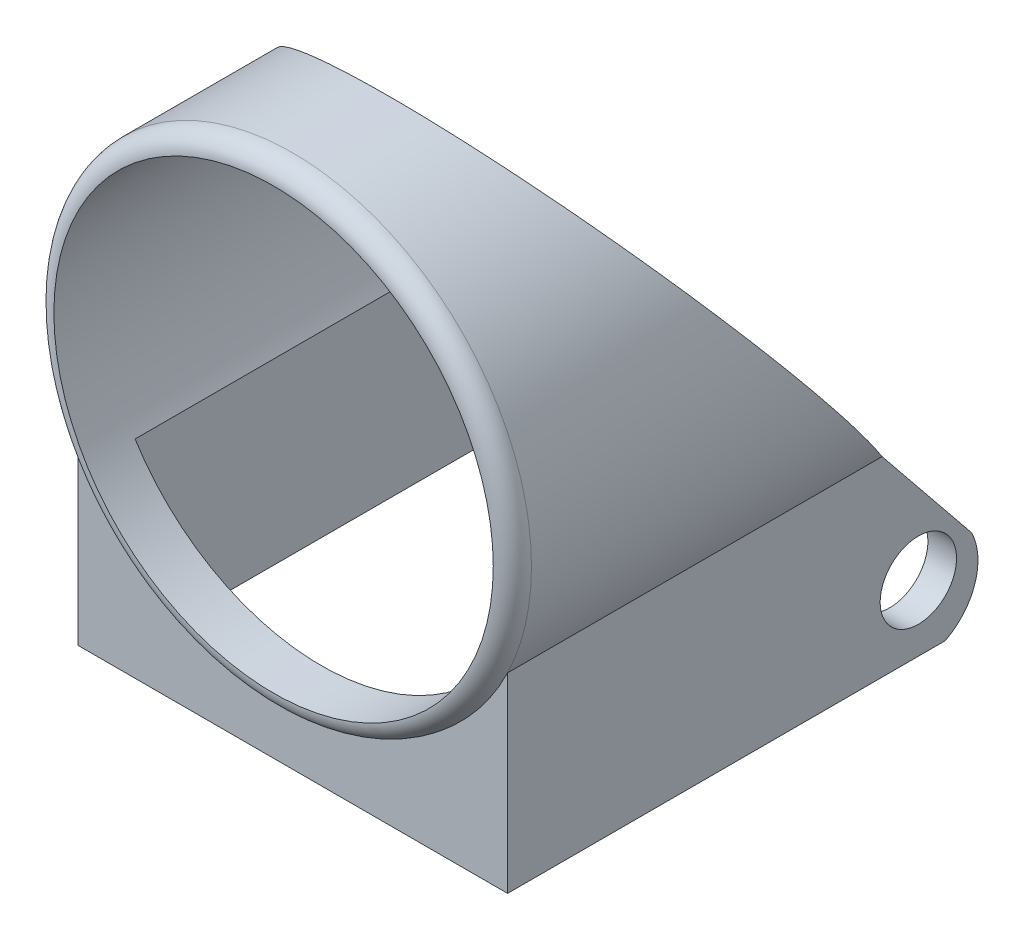
SolidWorks part; units mm, degrees
ref_plane "前视基准面" through (0, 0, 0) normal (0, 0, 1) x (1, 0, 0)
ref_plane "上视基准面" through (0, 0, 0) normal (0, 1, 0) x (1, 0, 0)
ref_plane "右视基准面" through (0, 0, 0) normal (1, 0, 0) x (0, 0, -1)
sketch "草图1" plane through (0, 0, 0) normal (0, 0, 1) x (1, 0, 0)
  line L0 (0, 0) -> (420.2148, 0) construction
  line L1 (420.2148, 0) -> (-452.8001, 0) construction
  line L3 (0, -30.8972) -> (0, -469.0928) construction
  line L5 (-22.5, -10.8972) -> (-22.5, -30.8972)
  line L6 (-22.5, -30.8972) -> (22.5, -30.8972)
  line L7 (22.5, -30.8972) -> (22.5, -10.8972)
  arc A0 (22.5, -10.8972) -> (-22.5, -10.8972) centre (0, 0) ccw
  dimension "D1" = 50
  dimension "D2" = 45
  dimension "D3" = 20
extrude "凸台-拉伸1" add sketch "草图1" along normal blind 50
shell "抽壳2" thickness 3 removed face at (0, -30.8972, 25) removed face at (0, -11.9229, 0)
sketch "草图13" plane through (0, 0, 0) normal (1, 0, 0) x (0, 0, -1)
  line L0 (-40, 25.2086) -> (-1.4323, -22.4712)
  line L2 (-4.1843, -30.8972) -> (0, -30.8972)
  line L6 (0, -30.8972) -> (0, 25.2086)
  line L9 (-50, 25) -> (-50, -10.8972) construction
  line L11 (0, 0) -> (-41.2704, 0) construction
  line L12 (-41.2704, 0) -> (-65.2649, 0) construction
  line L13 (0, 25.2086) -> (-40, 25.2086)
  line L15 (-50, -30.8972) -> (0, -30.8972) construction
  circle A0 centre (-7, -24) radius 4
  arc A1 (-4.1843, -30.8972) -> (-1.4323, -22.4712) centre (-7.0213, -25.3082) ccw
  point P10 (-50, 7.0514)
  dimension "D1" = 8
  dimension "D3" = 10
  dimension "D2" = 43
  dimension "D6" = 24
extrude "切除-拉伸1" cut sketch "草图13" against normal mid plane 500
sketch "草图18" plane through (0, 0, 50) normal (0, 0, 1) x (1, 0, 0)
  circle A0 centre (0, 0) radius 25
  dimension "D1" = 50
extrude "凸台-拉伸4" add sketch "草图18" along normal blind 2
fillet "圆角3" radius 2 1 edges at (25, 0, 52)
sketch "草图19" plane through (0, 0, 52) normal (0, 0, 1) x (1, 0, 0)
  circle A0 centre (0, 0) radius 9.1535
  dimension "30" = 18.307
extrude "切除-拉伸10" cut sketch "草图19" against normal through all
sketch "草图14" plane through (0, 0, 50) normal (0, 0, 1) x (1, 0, 0)
  circle A0 centre (0, 0) radius 15
  circle A1 centre (0, 0) radius 15
  dimension "D1" = 30
sketch "草图16" plane through (0, 0, 50) normal (0, 0, 1) x (1, 0, 0)
  circle A0 centre (0, 0) radius 25
  dimension "D1" = 50
extrude "凸台-拉伸3" add sketch "草图16" along normal blind 2
fillet "圆角2" radius 2 1 edges at (25, 0, 52)
sketch "草图17" plane through (0, 0, 52) normal (0, 0, 1) x (1, 0, 0)
  circle A0 centre (0, 0) radius 23
extrude "切除-拉伸9" cut sketch "草图17" against normal through all
